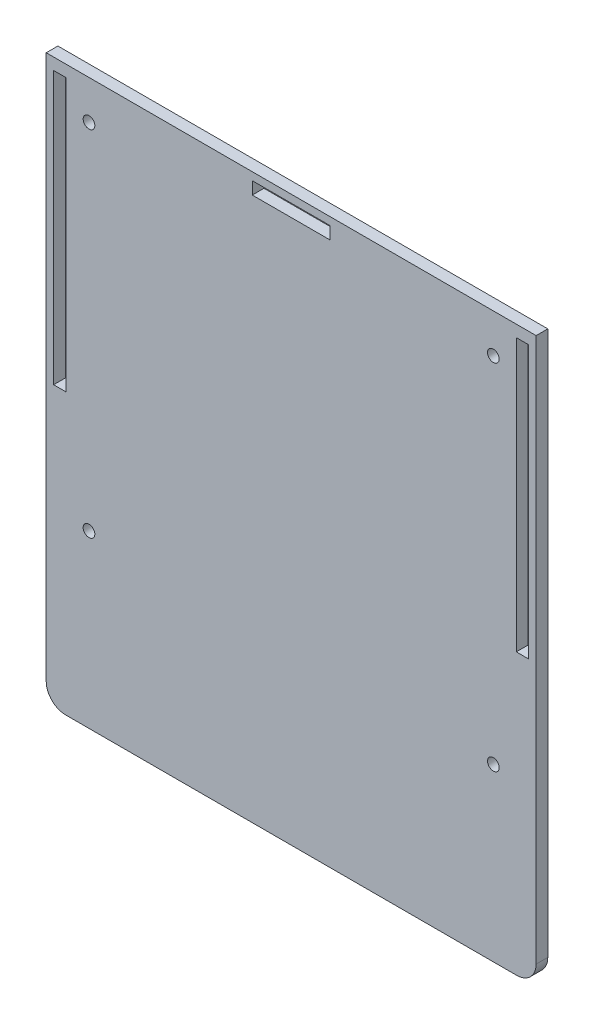
SolidWorks part; units mm, degrees
material "Maple"
ref_plane "Front Plane" through (0, 0, 0) normal (0, 0, 1) x (1, 0, 0)
ref_plane "Top Plane" through (0, 0, 0) normal (0, 1, 0) x (1, 0, 0)
ref_plane "Right Plane" through (0, 0, 0) normal (1, 0, 0) x (0, 0, -1)
sketch "Sketch1" plane through (0, 0, 0) normal (0, 0, 1) x (1, 0, 0)
  line L1 (-58, -75) -> (58, -75)
  line L5 (-63, 0) -> (63, 0) construction
  line L18 (-63, -70) -> (-63, 70)
  line L19 (-10, 68) -> (10, 68)
  line L20 (-10, 68) -> (-10, 64.8)
  line L21 (-10, 64.8) -> (10, 64.8)
  line L22 (10, 68) -> (10, 64.8)
  line L23 (-10, 68) -> (10, 64.8) construction
  line L24 (-10, 64.8) -> (10, 68) construction
  line L25 (63, 70) -> (63, -70)
  line L29 (-61.1, 67) -> (-61.1, -3)
  line L30 (-61.1, -3) -> (-57.9, -3)
  line L31 (-57.9, 67) -> (-57.9, -3)
  line L32 (-61.1, 67) -> (-57.9, -3) construction
  line L33 (-61.1, -3) -> (-57.9, 67) construction
  line L34 (-63, 32) -> (-59.5, 32) construction
  line L36 (57.9, 67) -> (57.9, -3)
  line L37 (57.9, -3) -> (61.1, -3)
  line L38 (61.1, 67) -> (61.1, -3)
  line L39 (57.9, 67) -> (61.1, -3) construction
  line L40 (57.9, -3) -> (61.1, 67) construction
  line L41 (-59.5, 32) -> (59.5, 32) construction
  line L42 (59.5, 32) -> (63, 32) construction
  line L46 (61.1, 67) -> (57.9, 67)
  line L47 (-61.1, 67) -> (-57.9, 67)
  line L48 (-63, 70) -> (63, 70)
  line L49 (-63, -31) -> (-52, -31) construction
  line L50 (-52, -31) -> (52, -31) construction
  line L51 (52, -31) -> (63, -31) construction
  arc A1 (63, -70) -> (58, -75) centre (58, -70) cw
  arc A2 (-58, -75) -> (-63, -70) centre (-58, -70) cw
  circle A3 centre (-52, -31) radius 1.5
  circle A4 centre (52, -31) radius 1.5
  circle A5 centre (52, 60) radius 1.5
  circle A6 centre (-52, 60) radius 1.5
  point P0 (0, 0)
  point P6 (-59.5, 32)
  point P12 (59.5, 32)
  point P16 (0, 66.4)
  point P22 (63, -75)
  point P31 (59.5, 67)
  point P32 (0, 0)
  point P34 (-63, -75)
  dimension "D7" = 145
  dimension "D6" = 5
  dimension "D10" = 104
  dimension "D11" = 3
  dimension "D1" = 126
  dimension "D2" = 3
  dimension "D3" = 20
  dimension "D4" = 3.2
  dimension "D5" = 3.5
  dimension "D8" = 70
  dimension "D9" = 2
  dimension "D12" = 10
  dimension "D13" = 91
extrude "Boss-Extrude1" add sketch "Sketch1" along normal blind 3
